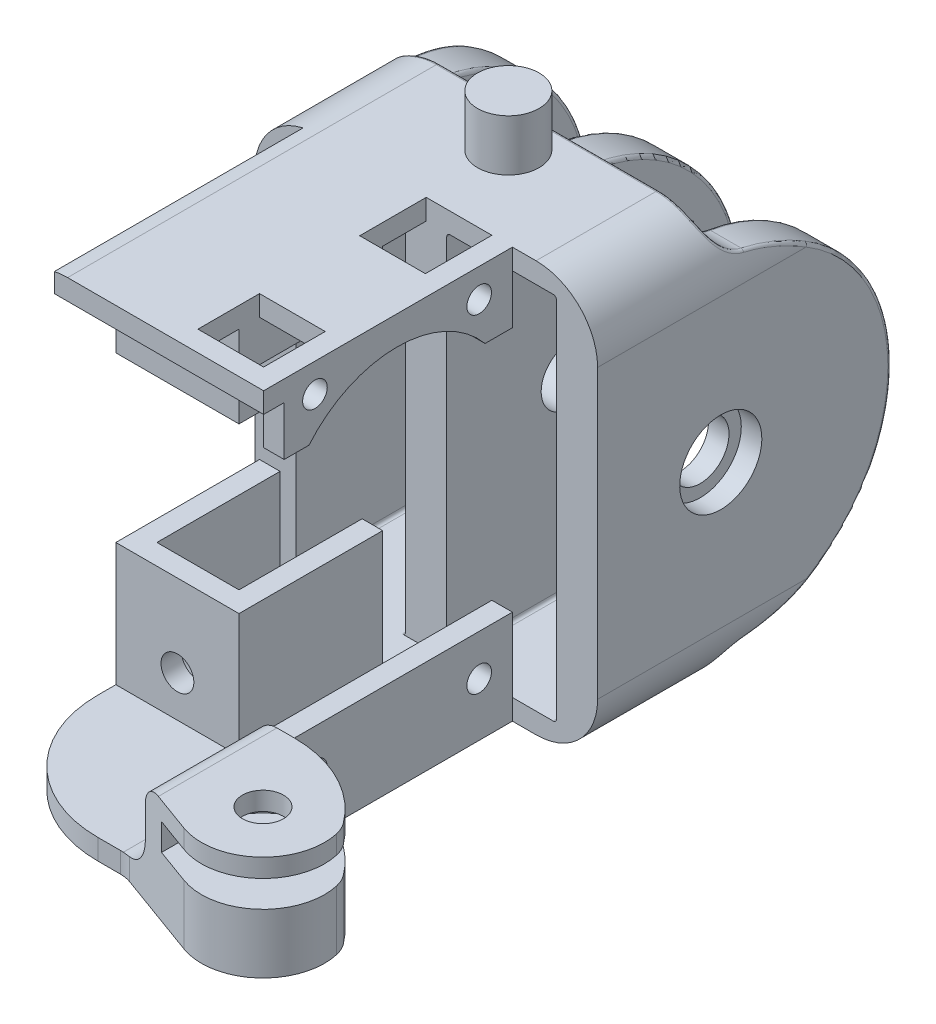
SolidWorks part; units mm, degrees
ref_plane "Front" through (0, 0, 0) normal (0, 0, 1) x (1, 0, 0)
ref_plane "Top" through (0, 0, 0) normal (0, 1, 0) x (1, 0, 0)
ref_plane "Right" through (0, 0, 0) normal (1, 0, 0) x (0, 0, -1)
sketch "Sketch1" plane through (0, 0, 0) normal (0, 0, 1) x (1, 0, 0)
  line L0 (8.35, -10) -> (8.35, 10)
  line L1 (-6.35, -8.5) -> (6.35, -8.5)
  line L2 (-6.35, -8.5) -> (-6.35, 8.5)
  line L3 (-6.35, 8.5) -> (6.35, 8.5)
  line L4 (6.35, -8.5) -> (6.35, 8.5)
  line L7 (-8.35, 10) -> (8.35, 10)
  line L8 (-8.35, -10) -> (-8.35, 10)
  line L9 (-8.35, -10) -> (8.35, -10)
  point P0 (0, 0)
  dimension "D1" = 20
  dimension "D4" = 16.7
extrude "Boss-Extrude1" add sketch "Sketch1" along normal blind 20 and the other way blind 12 contours L1 L4 L3 L2 | L8 L9 L0 L7 L4 L1 L2 L3 region at (0, -9.7394, 0) region at (0, 0, 0)
sketch "Sketch9" plane through (0, 10, 0) normal (0, 1, 0) x (1, 0, 0)
  circle A0 centre (0, 0) radius 1.5
  dimension "D1" = 3
extrude "Boss-Extrude4" add sketch "Sketch9" along normal blind 2.5
sketch "Sketch10" plane through (0, -10, 0) normal (0, -1, 0) x (1, 0, 0)
  circle A0 centre (0, 0) radius 1.5
  dimension "D1" = 3
extrude "Boss-Extrude5" add sketch "Sketch10" along normal blind 2.5 contours A0
sketch "Sketch73" plane through (0, 0, 0) normal (0, 1, 0) x (1, 0, 0)
  line L0 (9.6599, -17.7669) -> (4.8898, -4.6612)
  line L1 (0.0004, 0.0009) -> (0.0004, -19.9991) construction
  line L2 (0.0004, 0.0009) -> (6.8408, -18.7929) construction
  line L3 (5.8148, -21.612) -> (-4.1426, -17.9878)
  arc A0 (0.0004, -19.9991) -> (6.8408, -18.7929) centre (0.0004, 0.0009) ccw construction
  circle A1 centre (6.8408, -18.7929) radius 1
  circle A2 centre (6.8408, -18.7929) radius 3
  circle A3 centre (6.8408, -18.7929) radius 10
  dimension "D1" = 6
  dimension "D2" = 20
  dimension "D3" = 20
extrude "Extrude46" add sketch "Sketch73" along normal blind 10 and the other way blind 10 contours A2 A1 | L0 A3 L3 A2 | A1 region at (2.7313, 0, 14.6834) region at (9.7117, 0, 18.2867) region at (6.8408, 0, 18.7929)
extrude "Extrude52" cut sketch "Sketch" against normal through all both and the other way through all contours A0 A1 L2 | L2 A1 A0 region at (6.8408, 0, 18.7929)
sketch "Sketch" plane through (0, 0, 0) normal (0, 1, 0) x (1, 0, 0) same geometry as "Sketch73"
sketch "Sketch21" plane through (0, 0, 0) normal (1, 0, 0) x (0, 0, -1)
  line L0 (0, 0) -> (2, 0) construction
  line L1 (2, 0) -> (6.3301, 2.5) construction
  circle A0 centre (2, 0) radius 1.4
  circle A1 centre (6.3301, 2.5) radius 1.05
  circle A2 centre (2, 0) radius 5 construction
extrude "Extrude7" cut sketch "Sketch21" against normal through all both and the other way through all contours A0 L0 L1 | L0 A0 L1 region at (0, 0, -2)
sketch "Sketch23" plane through (0, 0, 0) normal (1, 0, 0) x (0, 0, -1)
  line L0 (2, 9.5) -> (2, 10)
  line L2 (2, -8.3) -> (2, -11.4416)
  line L4 (2, 11.5383) -> (19.1929, 11.5383)
  line L6 (2, 11.5383) -> (2, 10)
  line L7 (2, 8.3) -> (2, 9.5)
  line L8 (2, -11.4416) -> (19.1929, -11.4416)
  line L9 (2, -10.6179) -> (2, -8.3)
  line L10 (19.1929, 11.5383) -> (19.1929, -11.4416)
  circle A2 centre (2, 0) radius 4
  arc A4 (2, -8.3) -> (2, 8.3) centre (2, 0) ccw
extrude "Extrude8" cut sketch "Sketch23" against normal through all both and the other way through all contours L2 L6 L0 region at (0, 0.0666, -12.5103)
sketch "Sketch25" plane through (0, 0, 0) normal (1, 0, 0) x (0, 0, -1)
  circle A0 centre (2, 0) radius 2
extrude "Extrude9" cut sketch "Sketch25" along normal blind 10 from offset 7.35 contours A0 region at (0, 0, -2)
mirror "Mirror1" about plane through (0, 0, 0) normal (1, 0, 0) of "Extrude9"
sketch "Sketch26" plane through (-7.35, 0, 0) normal (-1, 0, 0) x (0, 0, 1)
  line L13 (-2, 2.3671) -> (-4.05, 1.1836)
  line L14 (-4.05, 1.1836) -> (-4.05, -1.1836)
  line L15 (-4.05, -1.1836) -> (-2, -2.3671)
  line L16 (-2, -2.3671) -> (0.05, -1.1836)
  line L17 (0.05, -1.1836) -> (0.05, 1.1836)
  line L18 (0.05, 1.1836) -> (-2, 2.3671)
  circle A0 centre (-2, 0) radius 2.05 construction
extrude "Extrude10" cut sketch "Sketch26" along normal blind 10
sketch "Sketch74" plane through (0, 0, 0) normal (0, 1, 0) x (1, 0, 0)
  line L0 (0, 0) -> (0, -13.12)
  line L2 (0, -13.12) -> (-35.0583, -13.12)
  line L3 (0, -13.12) -> (0, -42.3661)
  line L4 (0, -42.3661) -> (-35.0583, -42.3661)
  line L5 (-35.0583, -13.12) -> (-35.0583, -42.3661)
extrude "Extrude48" cut sketch "Sketch74" against normal blind 9 and the other way blind 9 contours L2 L5 L4 L3 region at (-17.5292, 0, 27.7431)
sketch "Sketch59" plane through (0, 0, 13.12) normal (0, 0, 1) x (1, 0, 0)
  line L0 (0, 0) -> (-13.8891, 0) construction
  line L13 (0, 0) -> (-3, 0)
  line L14 (-3, 0) -> (-3, -7)
  line L15 (0, 0) -> (0, -1.8329) construction
  line L31 (-3, 0) -> (-3, 7)
  circle A4 centre (-3, -7) radius 0.8
  circle A5 centre (-3, 7) radius 0.8
extrude "Extrude47" cut sketch "Sketch59" against normal through all contours A5 | A4 region at (-2.4503, -6.4503, 13.12) region at (-3.5497, 7.5497, 13.12)
sketch "Sketch75" plane through (0, 0, 0) normal (0, 1, 0) x (1, 0, 0)
  line L0 (0, 0) -> (0, -4)
  line L1 (0, -4) -> (-6, -4)
  line L3 (-6, -4) -> (-15.9073, -4)
  line L4 (-6, -4) -> (-6, -23.9043)
  line L5 (-6, -23.9043) -> (-15.9073, -23.9043)
  line L6 (-15.9073, -4) -> (-15.9073, -23.9043)
  dimension "D1" = 6
  dimension "D2" = 4
extrude "Extrude49" cut sketch "Sketch75" against normal blind 9 and the other way blind 9 contours L3 L6 L5 L4 region at (-10.9536, 0, 13.9522)
sketch "Sketch76" plane through (0, 0, 0) normal (0, 1, 0) x (1, 0, 0)
  line L0 (0, 0) -> (-1, 0)
  line L6 (0, 0) -> (0, 11.9912) construction
  line L12 (0, 0) -> (1, 0)
  line L22 (1, 0) -> (6.35, 0)
  line L23 (1, 0) -> (1, 12.217)
  line L24 (1, 12.217) -> (6.35, 12.217)
  line L25 (6.35, 0) -> (6.35, 12.217)
  line L26 (-1, 0) -> (-6.35, 0)
  line L27 (-1, 0) -> (-1, 13.0329)
  line L28 (-1, 13.0329) -> (-6.35, 13.0329)
  line L29 (-6.35, 0) -> (-6.35, 13.0329)
  line L30 (-1, 0) -> (-6.35, 0)
  line L31 (-1, 0) -> (-1, -6.12)
  line L32 (-1, -6.12) -> (-6.35, -6.12)
  line L33 (-6.35, 0) -> (-6.35, -6.12)
  line L34 (1, 0) -> (6.35, 0)
  line L35 (1, 0) -> (1, -6.12)
  line L36 (1, -6.12) -> (6.35, -6.12)
  line L37 (6.35, 0) -> (6.35, -6.12)
  dimension "D1" = 1
  dimension "D2" = 1
extrude "Extrude50" cut sketch "Sketch76" against normal blind 9 and the other way blind 9 contours L26 L33 L32 L31 | L29 L26 L27 L28 | L22 L25 L24 L23 | L37 L22 L35 L36 region at (-3.675, 0, 3.06) region at (-3.675, 0, -6.5165) region at (3.675, 0, -6.1085) region at (3.675, 0, 3.06)
sketch "Sketch83" plane through (0, 0, 0) normal (0, 1, 0) x (1, 0, 0)
  line L0 (0, 0) -> (0, -4)
  line L1 (0, 0) -> (0, -6.12)
  line L3 (0, -6.12) -> (2, -6.12)
  line L4 (0, -6.12) -> (0, -4)
  line L5 (0, -4) -> (2, -4)
  line L6 (2, -6.12) -> (2, -4)
  line L7 (0, -6.12) -> (-11.9079, -6.12)
  line L8 (0, -6.12) -> (0, -4)
  line L9 (0, -4) -> (-11.9079, -4)
  line L10 (-11.9079, -6.12) -> (-11.9079, -4)
  dimension "D1" = 4
  dimension "D2" = 2.12
extrude "Extrude56" cut sketch "Sketch83" against normal blind 9 and the other way blind 9 contours L10 L7 L1 L9 | L3 L6 L5 L1 region at (1, 0, 5.06) region at (-5.9539, 0, 5.06)
sketch "Sketch84" plane through (0, 0, 0) normal (0, 1, 0) x (1, 0, 0)
  line L0 (0, 0) -> (0, -6.12)
  line L1 (6.35, -6.12) -> (-6, -6.12) construction
  line L2 (0, -6.12) -> (6.35, -6.12)
  line L4 (0, -6.12) -> (0, -26.7548)
  line L5 (0, -26.7548) -> (2.85, -26.7548)
  line L6 (2.85, -18.793) -> (2.85, -26.7548)
  line L8 (2.85, -15.12) -> (2.85, -18.793)
  line L9 (0, 0) -> (0, -15.12)
  line L10 (2.85, -15.12) -> (6.35, -15.12)
  line L12 (6.35, -6.12) -> (6.35, -15.12)
  dimension "D1" = 6.12
  dimension "D2" = 6.35
  dimension "D3" = 3.5
  dimension "D4" = 9
extrude "Extrude57" cut sketch "Sketch84" against normal blind 9 and the other way blind 9 contours L2 L4 L5 L6 region at (2.5324, 0, 14.4083)
sketch "Sketch85" plane through (0, 0, 6.12) normal (0, 0, -1) x (-1, 0, 0)
  line L0 (1, 7) -> (0, 7)
  line L1 (0, 9) -> (0, -9) construction
  line L2 (0, 7) -> (0, 0)
  line L3 (0, 0) -> (6, 0)
  line L4 (6, 9) -> (6, -9) construction
  line L5 (6, 0) -> (6, 7)
  line L6 (6, 7) -> (5, 7)
  line L7 (1, -7) -> (1, -3)
  line L8 (1, -3) -> (0, -3)
  line L9 (0, -3) -> (0, 0)
  line L10 (5, -7) -> (5, -3)
  line L11 (5, -3) -> (6, -3)
  line L12 (6, -3) -> (6, 0)
  circle A0 centre (3, -7) radius 2
  circle A1 centre (3, 7) radius 2
  circle M1 centre (3, -7) radius 0.8
  circle M2 centre (3, 7) radius 0.8
  line M3 (0, 9) -> (0, -9)
  line M5 (6, -9) -> (6, 9)
extrude "Extrude58" cut sketch "Sketch85" against normal blind 6 contours A0 L10 L11 L3 L8 L7 M5 M3 | A1 L0 L3 L6 M3 M5 | A1 M2 | A0 M1 region at (-3, 3.0336, 6.12) region at (-3, 8.9434, 6.12) region at (-3, -2.466, 6.12) region at (-3, -5.0566, 6.12)
sketch "Sketch86" plane through (0, 0, 12.12) normal (0, 0, -1) x (-1, 0, 0)
  line L1 (0, 0) -> (6, 0)
  line L2 (0, 0) -> (0, -3)
  line L3 (0, -3) -> (6, -3)
  line L4 (6, 0) -> (6, -3)
  line L5 (0, 0) -> (6, 0)
  line L6 (0, 0) -> (0, 5)
  line L7 (0, 5) -> (6, 5)
  line L8 (6, 0) -> (6, 5)
  line M12 (5, -3) -> (6, -3)
  line M13 (6, -3) -> (6, 7)
  line M17 (0, 7) -> (0, -3)
  line M18 (0, -3) -> (1, -3)
extrude "Extrude59" cut sketch "Sketch86" against normal blind 1 contours L3 L1 M18 M12 M13 M17 | L7 L1 M17 M13 region at (-3, 2.5, 12.12) region at (-3, -1.5, 12.12)
sketch "Sketch87" plane through (0, 0, 0) normal (0, 0, 1) x (1, 0, 0)
  line L0 (0, 0) -> (0, 2.5)
  line L2 (0, 2.5) -> (15, 2.5)
  line L3 (0, 2.5) -> (0, 9)
  line L4 (0, 9) -> (15, 9)
  line L5 (15, 2.5) -> (15, 9)
  line L6 (0, 2.5) -> (15, 2.5)
  line L7 (0, 2.5) -> (0, -4.9)
  line L8 (0, -4.9) -> (15, -4.9)
  line L9 (15, 2.5) -> (15, -4.9)
  dimension "D1" = 2.5
  dimension "D2" = 6.5
  dimension "D3" = 7.4
extrude "Extrude60" cut sketch "Sketch87" along normal through all from offset 4 contours L9 L2 L0 L7 L8 | L2 L5 L4 L3 region at (7.5, -1.2, 0) region at (7.5, 5.75, 0)
sketch "Sketch89" plane through (0, 0, 0) normal (1, 0, 0) x (0, 0, -1)
  line L0 (0, 0) -> (0, 5.4564) construction
  line L1 (2, 0) -> (2, 4.1188) construction
  line L2 (2, 0) -> (-1002.016, 0) construction
  line L3 (-9.62, 3) -> (-9.62, -6.2769) construction
  line L4 (-5.62, 3) -> (-13.62, 3)
  line L5 (-13.62, 3) -> (-13.62, 8.6)
  line L6 (-13.62, 3) -> (-13.62, -7.4)
  line L7 (-5.62, 3) -> (-5.62, -7.4)
  line L8 (-5.62, 3) -> (-5.62, 8.6)
  circle A0 centre (-9.62, 3) radius 1.5
  dimension "D1" = 10.4
  dimension "D2" = 5.6
  dimension "D3" = 4
sketch "Sketch90" plane through (0, 0, 0) normal (1, 0, 0) x (0, 0, -1)
  line L1 (-9.62, 3) -> (-15.12, 3)
  line L2 (-9.62, 3) -> (-9.62, 13)
  line L3 (-9.62, 13) -> (-15.12, 13)
  line L4 (-15.12, 3) -> (-15.12, 13)
  line L5 (-9.62, 3) -> (-4, 3)
  line L6 (-9.62, 3) -> (-9.62, 13)
  line L7 (-9.62, 13) -> (-4, 13)
  line L8 (-4, 3) -> (-4, 13)
  line L9 (-9.62, 3) -> (-15.12, 3)
  line L10 (-9.62, 3) -> (-9.62, -12)
  line L11 (-9.62, -12) -> (-15.12, -12)
  line L12 (-15.12, 3) -> (-15.12, -12)
  line L13 (-9.62, 3) -> (-4, 3)
  line L14 (-9.62, 3) -> (-9.62, -12)
  line L15 (-9.62, -12) -> (-4, -12)
  line L16 (-4, 3) -> (-4, -12)
  dimension "D1" = 5.5
  dimension "D2" = 5.62
extrude "Extrude61" cut sketch "Sketch90" along normal through all from offset 4.2 contours L4 L1 L2 L3 | L5 L8 L7 L2 | L1 L12 L11 L10 | L16 L5 L10 L14 L15 region at (0, -4.5, 12.37) region at (0, 8, 12.37) region at (0, 8, 6.81) region at (0, -4.5, 6.81)
sketch "Sketch92" plane through (0, 0, 0) normal (1, 0, 0) x (0, 0, -1)
  line L1 (-15.12, 10) -> (-4, 10)
  line L2 (-15.12, 10) -> (-15.12, -10)
  line L3 (-15.12, -10) -> (-4, -10)
  line L4 (-4, 10) -> (-4, -10)
extrude "Extrude62" add sketch "Sketch92" against normal blind 1 from offset 4.2
sketch "Sketch93" plane through (0, 0, 0) normal (1, 0, 0) x (0, 0, -1)
  circle A0 centre (-13.62, 8.6) radius 0.6
  circle A1 centre (-5.62, 8.6) radius 0.6
  circle A2 centre (-5.62, -7.4) radius 0.6
  circle A3 centre (-13.62, -7.4) radius 0.6
extrude "Extrude63" cut sketch "Sketch93" against normal blind 2 from offset 4.2
sketch "Sketch96" plane through (0, 0, 0) normal (1, 0, 0) x (0, 0, -1)
  line L1 (-12.12, 6.6) -> (-15.12, 6.6)
  line L2 (-12.12, 6.6) -> (-12.12, 10.6)
  line L3 (-12.12, 10.6) -> (-15.12, 10.6)
  line L4 (-15.12, 6.6) -> (-15.12, 10.6)
  line L5 (-12.12, 6.6) -> (-15.12, 10.6) construction
  line L6 (-12.12, 10.6) -> (-15.12, 6.6) construction
  line L7 (-7.24, 6.6) -> (-4, 6.6)
  line L8 (-7.24, 6.6) -> (-7.24, 10.6)
  line L9 (-7.24, 10.6) -> (-4, 10.6)
  line L10 (-4, 6.6) -> (-4, 10.6)
  line L11 (-7.24, 6.6) -> (-4, 10.6) construction
  line L12 (-7.24, 10.6) -> (-4, 6.6) construction
  line L13 (-12.12, -12.4) -> (-15.12, -12.4)
  line L14 (-12.12, -12.4) -> (-12.12, -2.4)
  line L15 (-12.12, -2.4) -> (-15.12, -2.4)
  line L16 (-15.12, -12.4) -> (-15.12, -2.4)
  line L17 (-12.12, -12.4) -> (-15.12, -2.4) construction
  line L18 (-12.12, -2.4) -> (-15.12, -12.4) construction
  line L19 (-4, -12.4) -> (-7.24, -12.4)
  line L20 (-4, -12.4) -> (-4, -2.4)
  line L21 (-4, -2.4) -> (-7.24, -2.4)
  line L22 (-7.24, -12.4) -> (-7.24, -2.4)
  line L23 (-4, -12.4) -> (-7.24, -2.4) construction
  line L24 (-4, -2.4) -> (-7.24, -12.4) construction
  point P0 (-13.62, 8.6)
  point P6 (-5.62, 8.6)
  point P12 (-13.62, -7.4)
  point P18 (-5.62, -7.4)
  dimension "D1" = 3
  dimension "D2" = 4
  dimension "D3" = 3.24
  dimension "D4" = 4
  dimension "D5" = 3
  dimension "D6" = 10
  dimension "D7" = 3.24
  dimension "D8" = 10
extrude "Extrude64" cut sketch "Sketch96" against normal blind 3.2 from offset 3.2
sketch "Sketch97" plane through (0, 0, 0) normal (1, 0, 0) x (0, 0, -1)
  line L0 (-5.62, 3) -> (-13.62, 3) construction
  line L1 (-9.62, 3) -> (-9.62, 6.6)
  line L2 (0, 0) -> (-1.1503, 0) construction
  line L3 (-9.62, 6.6) -> (-4, 6.6)
  line L4 (-4, -9) -> (-4, 9) construction
  line L5 (-4, 6.6) -> (-4, -11.5902)
  line L6 (-9.62, 6.6) -> (-15.12, 6.6)
  line L7 (-15.12, 9) -> (-15.12, -4.9) construction
  line L8 (-15.12, 6.6) -> (-15.12, -12.9504)
  line L9 (-9.62, 3) -> (-9.62, -5.4)
  line L10 (0, 0) -> (0, 6.2221) construction
  line L11 (-9.62, -5.4) -> (-15.12, -5.4)
  line L12 (-9.62, -5.4) -> (-4, -5.4)
  line L13 (2, 0) -> (2, 5.7085) construction
  circle A1 centre (-9.62, 3) radius 5.6
extrude "Extrude65" cut sketch "Sketch97" against normal blind 1 from offset 4.2 contours A1 L8 L11 L9 | A1 L9 L12 L5 L3 | L9 A1 L3 L1 | L6 A1 L8 L9 L1 | L3 A1 L6 | A1 L6 L8 region at (0, 2.3904, 12.086) region at (0, 2.3924, 7.144) region at (0, 7.4137, 9.62) region at (0, -2.6149, 6.211) region at (0, -3.2628, 12.8039) region at (0, 5.8626, 14.7552)
sketch "Sketch98" plane through (0, 0, 0) normal (0, 1, 0) x (1, 0, 0)
  line L0 (4.0908, -18.7929) -> (4.0908, -22.9688)
  line L1 (6.8408, -16.0429) -> (11.0167, -16.0429)
  circle A0 centre (6.8408, -18.7929) radius 2.75
  arc A1 (4.0908, -22.9688) -> (11.0167, -16.0429) centre (6.8408, -18.7929) ccw
  dimension "D1" = 5
  dimension "D2" = 5.5
extrude "Extrude66" cut sketch "Sketch98" along normal blind 1.2 and the other way blind 0.1 from offset 7 contours L0 A1 L1 A0 | A0 region at (6.8408, 0, 21.6526) region at (6.8408, 0, 18.7929) offset against normal yes
sketch "Sketch99" plane through (0, 0, 0) normal (0, 1, 0) x (1, 0, 0)
  line L0 (-6.35, -4) -> (-6, -4)
  line L1 (0, 0) -> (-6.35, 0)
  line L2 (-6.35, 0) -> (-6.35, -4)
  line L3 (-6, -4) -> (-6, -22.0258)
  line L4 (-6, -22.0258) -> (-14.9452, -22.0258)
  line L5 (-14.9452, -22.0258) -> (-14.9452, -4)
  line L6 (-14.9452, -4) -> (-6.35, -4)
extrude "Extrude67" cut sketch "Sketch99" along normal through all and the other way through all contours L6 L5 L4 L3 L0 region at (-10.4726, 0, 13.0129)
sketch "Sketch102" plane through (0, 0, 0) normal (1, 0, 0) x (0, 0, -1)
  line L1 (2, 0) -> (6.3301, 2.5) construction
  circle A0 centre (2, 0) radius 1.4
  circle A1 centre (6.3301, 2.5) radius 1.05
  circle A2 centre (2, 0) radius 5 construction
extrude "Extrude70" cut sketch "Sketch102" against normal through all and the other way blind 2
fillet "Fillet1" radius 3 4 edges at (-8.35, -10, 1) (8.35, -10, 1) (-8.35, 10, 1) (8.35, 10, 1)
fillet "Fillet2" radius 1.6 2 edges at (0, -8.3, -2) (7.2019, 8.3, -2)
fillet "Fillet3" radius 0.16 8 edges at (1, -9, 0.9013) (-1, -9, 0.9013) (6.35, 9, 0.9013) (-1, 9, 0.9013) (1, 9, 0.9013) (-6.35, 9, 0.9013) (-6.35, -9, 0.9013) (6.35, -9, 0.9013)
fillet "Fillet4" radius 0.16 40 edges at (7.6239, -8.9569, -2.2219) (5.9376, -9.9419, -2) (0, -10, -2) (-5.9376, -9.9419, -2) (-7.6371, -8.9415, -2.2311) (-8.35, 0, -10.3) (-7.6239, 8.9569, -2.2219) (-5.9376, 9.9419, -2) (0, 10, -2) (5.9376, 9.9419, -2) (7.6371, 8.9415, -2.2311) (-1.0698, -8.9721, -2.213) (-1, -8.4113, -2.7549) (-1, 0, -10.3) (-1, 8.4113, -2.7549) (-1.0453, 8.9515, -2.2251) (-3.675, 9, -2.1974) (-6.2802, 8.9721, -2.213) (-6.35, 8.4113, -2.7549) (-6.35, 0, -10.3) (-6.35, -8.4113, -2.7549) (-6.3047, -8.9515, -2.2251) (6.2802, -8.9721, -2.213) (6.35, -8.4113, -2.7549) (6.35, 0, -10.3) (6.35, 8.4113, -2.7549) (6.3047, 8.9515, -2.2251) (3.675, 9, -2.1974) (1.0698, 8.9721, -2.213) (1, 8.4113, -2.7549) (1, 0, -10.3) (1, -8.4113, -2.7549) (1.0453, -8.9515, -2.2251) (8.35, 0, -10.3) (-3.675, -9, -2.1974) (3.675, -9, -2.1974)
sketch "Sketch104" plane through (0, 0, 0) normal (0, 1, 0) x (1, 0, 0)
  line L0 (0, 0) -> (0, -16.12)
  line L2 (0, -16.12) -> (-13.0823, -16.12)
  line L3 (0, -16.12) -> (0, -21.4119)
  line L4 (0, -21.4119) -> (-13.0823, -21.4119)
  line L5 (-13.0823, -16.12) -> (-13.0823, -21.4119)
  line L6 (0, -16.12) -> (4.2, -16.12)
  line L7 (0, -16.12) -> (0, -22.7033)
  line L8 (0, -22.7033) -> (4.2, -22.7033)
  line L9 (4.2, -16.12) -> (4.2, -22.7033)
  line L10 (4.2, -16.12) -> (14.8583, -16.12)
  line L11 (4.2, -16.12) -> (4.2, -11.241)
  line L12 (4.2, -11.241) -> (14.8583, -11.241)
  line L13 (14.8583, -16.12) -> (14.8583, -11.241)
  line L14 (4.2, -16.12) -> (15.7844, -16.12)
  line L15 (4.2, -16.12) -> (4.2, -24.1026)
  line L16 (4.2, -24.1026) -> (15.7844, -24.1026)
  line L17 (15.7844, -16.12) -> (15.7844, -24.1026)
extrude "Extrude72" cut sketch "Sketch104" along normal through all contours L2 L5 L4 L3 | L9 L6 L3 L7 L8 | L17 L14 L10 L9 L15 L16 | L10 L13 L12 L11 region at (-6.5411, 0, 18.7659) region at (2.1, 0, 19.4117) region at (9.9922, 0, 20.1113) region at (9.5292, 0, 13.6805)
sketch "Sketch103" plane through (0, -10, 0) normal (0, -1, 0) x (1, 0, 0)
  line L1 (6.8408, 20.7559) -> (5.1408, 19.7744)
  line L2 (5.1408, 19.7744) -> (5.1408, 17.8115)
  line L3 (5.1408, 17.8115) -> (6.8408, 16.83)
  line L4 (6.8408, 16.83) -> (8.5408, 17.8115)
  line L5 (8.5408, 17.8115) -> (8.5408, 19.7744)
  line L6 (8.5408, 19.7744) -> (6.8408, 20.7559)
  circle A0 centre (6.8408, 18.7929) radius 1.7 construction
extrude "Extrude71" cut sketch "Sketch103" against normal blind 2.5
fillet "Fillet8" radius 6 1 edges at (-6, -9.4644, 20)
fillet "Fillet9" radius 1.6 1 edges at (1.3858, -9.5, 20)
fillet "Fillet10" radius 1.6 1 edges at (2.85, -9, 17.8265)
fillet "Fillet11" radius 1 1 edges at (2.85, -4.9, 17.8265)
sketch "Sketch105" plane through (1, 0, 0) normal (1, 0, 0) x (0, 0, -1)
  line L1 (6.3301, 4.463) -> (4.6301, 3.4815)
  line L2 (4.6301, 3.4815) -> (4.6301, 1.5185)
  line L3 (4.6301, 1.5185) -> (6.3301, 0.537)
  line L4 (6.3301, 0.537) -> (8.0301, 1.5185)
  line L5 (8.0301, 1.5185) -> (8.0301, 3.4815)
  line L6 (8.0301, 3.4815) -> (6.3301, 4.463)
  circle A0 centre (6.3301, 2.5) radius 1.7 construction
extrude "Extrude73" cut sketch "Sketch105" against normal blind 1.5
sketch "Sketch106" plane through (0, 0, 0) normal (1, 0, 0) x (0, 0, -1)
  circle A0 centre (6.3301, 2.5) radius 1.7
extrude "Extrude74" cut sketch "Sketch106" against normal through all from offset 7 offset against normal yes
fillet "Fillet12" radius 6 1 edges at (8.6965, -7.45, 15.12)
fillet "Fillet13" radius 1.6 2 edges at (9.6599, -8.55, 17.7669) (9.6599, -5.35, 17.7669)
